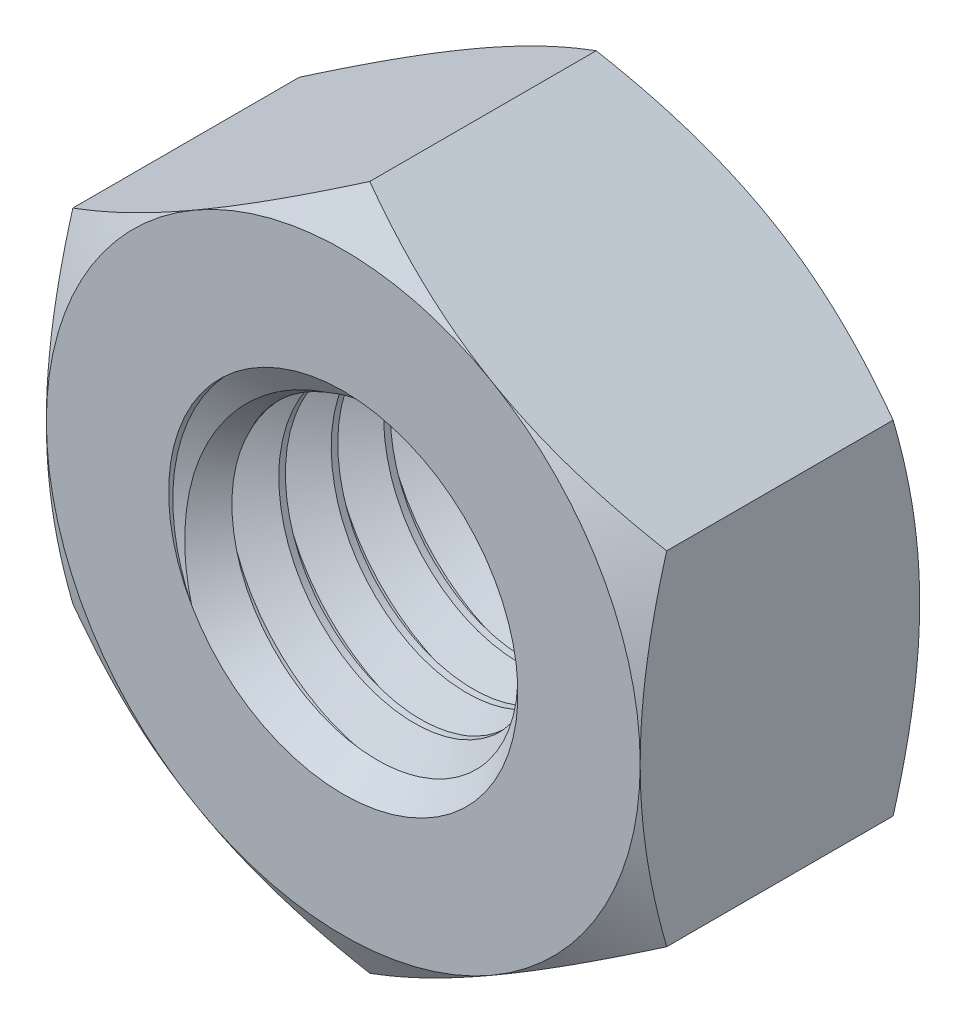
SolidWorks part; units mm, degrees
ref_plane "Front" through (0, 0, 0) normal (0, 0, 1) x (1, 0, 0)
ref_plane "Top" through (0, 0, 0) normal (0, 1, 0) x (1, 0, 0)
ref_plane "Right" through (0, 0, 0) normal (1, 0, 0) x (0, 0, -1)
sketch "Sketch1" plane through (0, 0, 0) normal (0, 0, 1) x (1, 0, 0)
  line L1 (-8.5, 4.9075) -> (-8.5, -4.9075)
  line L2 (-8.5, -4.9075) -> (0, -9.815)
  line L3 (0, -9.815) -> (8.5, -4.9075)
  line L4 (8.5, -4.9075) -> (8.5, 4.9075)
  line L5 (8.5, 4.9075) -> (0, 9.815)
  line L6 (0, 9.815) -> (-8.5, 4.9075)
  circle A0 centre (0, 0) radius 8.5 construction
  circle A1 centre (0, 0) radius 5 construction
  point P10 (0, 5)
  dimension "hex" = 17
  dimension "dia" = 10
extrude "Extrude1" add sketch "Sketch1" along normal mid plane 8
sketch "Sketch4" plane through (0, 0, -4) normal (0, 0, -1) x (-1, 0, 0)
  circle A0 centre (0, 0) radius 5 construction
  circle A1 centre (0, 0) radius 5
sketch "Sketch10" plane through (0, 0, 4) normal (0, 0, 1) x (1, 0, 0)
  circle A0 centre (0, 0) radius 5 construction
  circle A1 centre (0, 0) radius 5
extrude "Cut-Extrude2" cut sketch "Sketch10" against normal through all draft 45
sketch "Sketch11" plane through (0, 0, -4) normal (0, 0, -1) x (-1, 0, 0)
  circle A0 centre (0, 0) radius 5 construction
  circle A1 centre (0, 0) radius 5
extrude "Cut-Extrude3" cut sketch "Sketch11" against normal through all draft 45
sketch "Sketch13" plane through (0, 0, -4) normal (0, 0, -1) x (-1, 0, 0)
  circle A0 centre (0, 0) radius 5 construction
  circle A1 centre (0, 0) radius 5
extrude "Boss-Extrude1" add sketch "Sketch13" against normal up to vertex (8 mm away) separate body up to point (-8.5, 4.9075, 4)
curve "Helix/Spiral3" pitch 1.5 height 8 turns 5.3333
sketch "Sketch12" plane through (0, 0, 0) normal (1, 0, 0) x (0, 0, -1)
  line L0 (5.3125, 5) -> (4, 5)
  line L1 (5.3125, 5) -> (4.75, 4.0257)
  line L2 (4.75, 4.0257) -> (4.5625, 4.0257)
  line L3 (4.5625, 4.0257) -> (4, 5)
  line L4 (4.6562, 4.0257) -> (4.6563, 5) construction
  line L5 (4.2812, 4.5129) -> (5.0312, 4.5129) construction
  dimension "D1" = 60
  dimension "D2" = 0.1875
  dimension "D3" = 0.75
sweep "Cut-Sweep1" cut profiles "Sketch12" path "Helix/Spiral3"
combine bodies "Combine1" operation type subtract main body 116 bodies to subtract 118
sketch "Sketch7" plane through (0, 0, 4) normal (0, 0, 1) x (1, 0, 0)
  circle A0 centre (0, 0) radius 8.5 construction
  circle A1 centre (0, 0) radius 8.5
extrude "Extrude2" cut sketch "Sketch7" against normal blind 25.4 draft 60 flip side to cut
mirror "Mirror2" about plane through (0, 0, 0) normal (0, 0, 1) of "Extrude2"
sketch "Sketch8" plane through (0, 0, 4) normal (0, 0, 1) x (1, 0, 0)
  line L0 (-3.5355, 3.5355) -> (0, 0) construction
  line L1 (0, -4.8725) -> (0, 4.8725) construction
  circle A1 centre (0, 0) radius 5 construction
  point P0 (-3.5355, 3.5355)
  dimension "D1" = 45
sketch "Sketch14" plane through (0, 0, 4) normal (0, 0, 1) x (1, 0, 0)
  line L0 (0, 0) -> (-5, 0) construction
  arc A0 (0, 5) -> (-4.3376, -2.487) centre (0, 0) ccw construction
equation "\"D3@Helix/Spiral3\" = \"length@Extrude1\" "
equation "\"D2@Sketch12\" = \"D4@Helix/Spiral3\"*.125"
equation "\"D3@Sketch12\" = \"D4@Helix/Spiral3\"*.50"
